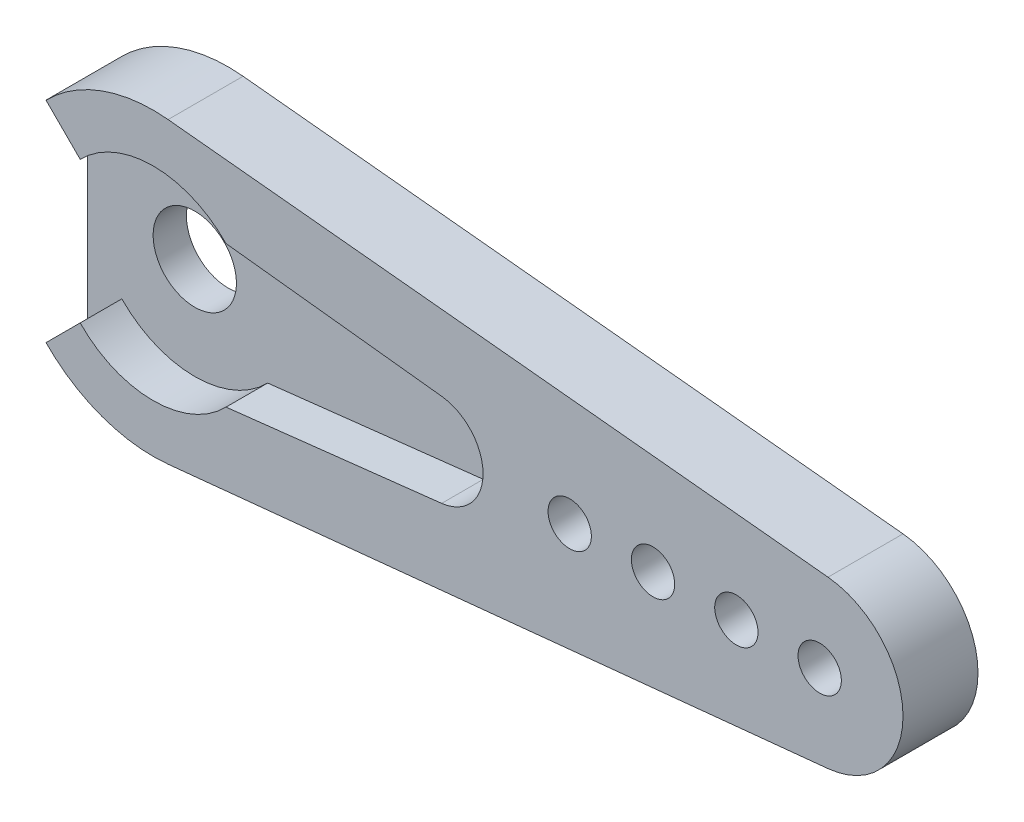
SolidWorks part; units mm, degrees
ref_plane "Front Plane" through (0, 0, 0) normal (0, 0, 1) x (1, 0, 0)
ref_plane "Top Plane" through (0, 0, 0) normal (0, 1, 0) x (1, 0, 0)
ref_plane "Right Plane" through (0, 0, 0) normal (1, 0, 0) x (0, 0, -1)
ref_axis "Axis1" through (58.0713, 0, 0) along (-1, 0, 0)
sketch "Esquisse1" plane through (0, 0, 0) normal (0, 0, 1) x (1, 0, 0)
  line L0 (-4.3758, 4.25) -> (-6.4265, 6.3008)
  line L1 (4.3758, 4.25) -> (17.3156, 2.7822)
  line L2 (17.3156, -2.7822) -> (4.3758, -4.25)
  line L4 (0.9, 8.9549) -> (40.5, 4.9749)
  line L5 (0.9, -8.9549) -> (40.5, -4.9749)
  line L6 (-4.3758, -4.25) -> (-6.4265, -6.3008)
  arc A0 (4.3758, 4.25) -> (-4.3758, 4.25) centre (0, 0) ccw
  arc A1 (17.3156, -2.7822) -> (17.3156, 2.7822) centre (17, 0) ccw
  arc A2 (4.3758, -4.25) -> (-4.3758, -4.25) centre (0, 0) cw
  arc A3 (-6.4265, 6.3008) -> (0.9, 8.9549) centre (0, 0) cw
  arc A4 (40.5, 4.9749) -> (40.5, -4.9749) centre (40, 0) cw
  arc A5 (-6.4265, -6.3008) -> (0.9, -8.9549) centre (0, 0) ccw
  dimension "D2" = 6.1
  dimension "D3" = 2.8
  dimension "D6" = 9
  dimension "D8" = 5
  dimension "D1" = 8.5
  dimension "D4" = 17
  dimension "D7" = 40
extrude "Main" add sketch "Esquisse1" along normal blind 2.5
sketch "Esquisse2" plane through (0, 0, 0) normal (0, 0, -1) x (-1, 0, 0)
  line L0 (-0.9, -8.9549) -> (-40.5, -4.9749)
  line L1 (-0.9, -8.9549) -> (-40.5, -4.9749) construction
  line L3 (-0.9, 8.9549) -> (-40.5, 4.9749)
  line L4 (6.4265, -6.3008) -> (6.4265, 6.3008)
  arc A0 (-40.5, 4.9749) -> (-40.5, -4.9749) centre (-40, 0) ccw construction
  arc A1 (-0.9, -8.9549) -> (6.4265, -6.3008) centre (0, 0) ccw
  circle A2 centre (0, 0) radius 2.5
  arc A3 (6.4265, 6.3008) -> (-0.9, 8.9549) centre (0, 0) ccw
  arc A5 (-40.5, 4.9749) -> (-40.5, -4.9749) centre (-40, 0) ccw
  arc A6 (-0.9, -8.9549) -> (6.4265, -6.3008) centre (0, 0) ccw construction
  dimension "D1" = 5
extrude "OriginalBracket" add sketch "Esquisse2" along normal blind 2
sketch "Esquisse3" plane through (0, 0, 2.5) normal (0, 0, 1) x (1, 0, 0)
  circle A0 centre (40, 0) radius 1.3
  arc A2 (40.5, -4.9749) -> (40.5, 4.9749) centre (40, 0) ccw construction
  dimension "D1" = 2.6
extrude "FixingHole" cut sketch "Esquisse3" against normal through all
pattern_linear "LPattern1" count 4 spacing 5 along (-1, 0, 0) of "FixingHole"
